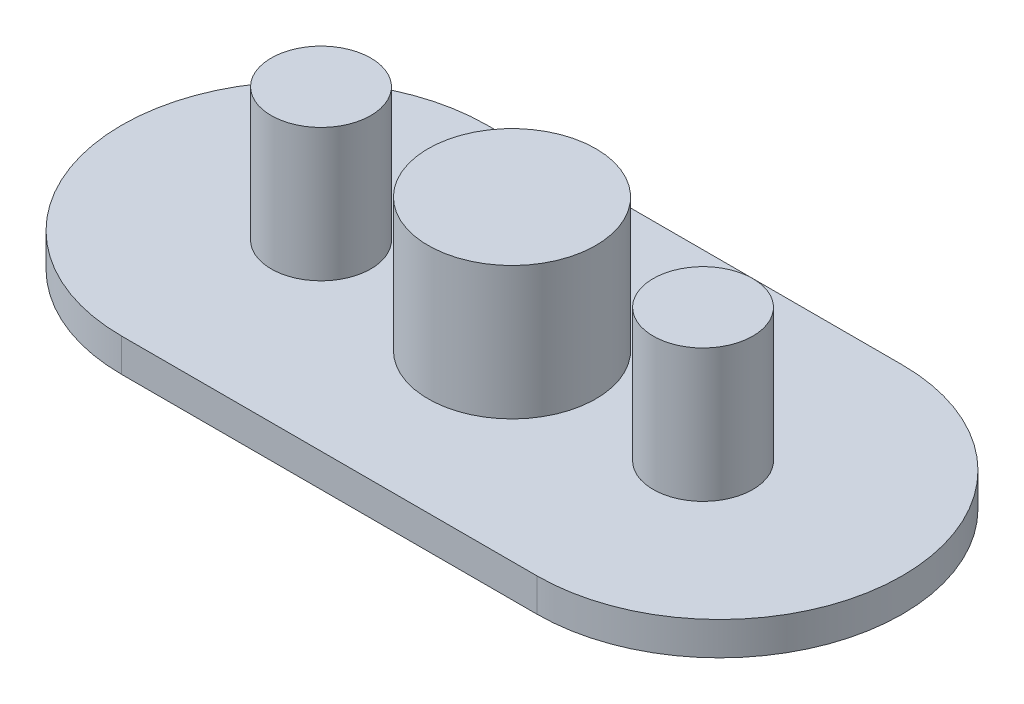
SolidWorks part; units mm, degrees
ref_plane "Front Plane" through (0, 0, 0) normal (0, 0, 1) x (1, 0, 0)
ref_plane "Top Plane" through (0, 0, 0) normal (0, 1, 0) x (1, 0, 0)
ref_plane "Right Plane" through (0, 0, 0) normal (1, 0, 0) x (0, 0, -1)
ref_axis "Axis1" through (-33.0333, 0, 0) along (1, 0, 0)
ref_axis "Axis2" through (0, 24.5224, 0) along (0, -1, 0)
ref_axis "Axis3" through (0, 0, -30.7663) along (0, 0, 1)
sketch "Sketch13" plane through (-28.226, 0, 0) normal (0, -1, 0) x (-1, 0, 0)
  line L0 (-40.726, 0) -> (-15.726, 0) construction
  line L2 (-40.726, 11) -> (-15.726, 11)
  line L3 (-40.726, -11) -> (-15.726, -11)
  arc A0 (-40.726, 11) -> (-40.726, -11) centre (-40.726, 0) ccw
  arc A1 (-15.726, -11) -> (-15.726, 11) centre (-15.726, 0) ccw
  point P4 (-28.226, 0)
  dimension "D3" = 25
  dimension "D4" = 22
extrude "Boss-Extrude10" add sketch "Sketch13" along normal blind 2 separate body
sketch "Sketch14" plane through (0, 0, 0) normal (0, -1, 0) x (1, 0, 0)
  line L0 (-11.5, 0) -> (11.5, 0) construction
  circle A0 centre (-11.5, 0) radius 3
  circle A1 centre (0, 0) radius 5.05
  circle A2 centre (11.5, 0) radius 3
  point P2 (0, 0)
  dimension "D2" = 10.1
  dimension "D3" = 6
  dimension "D1" = 23
extrude "Boss-Extrude11" add sketch "Sketch14" against normal blind 8
